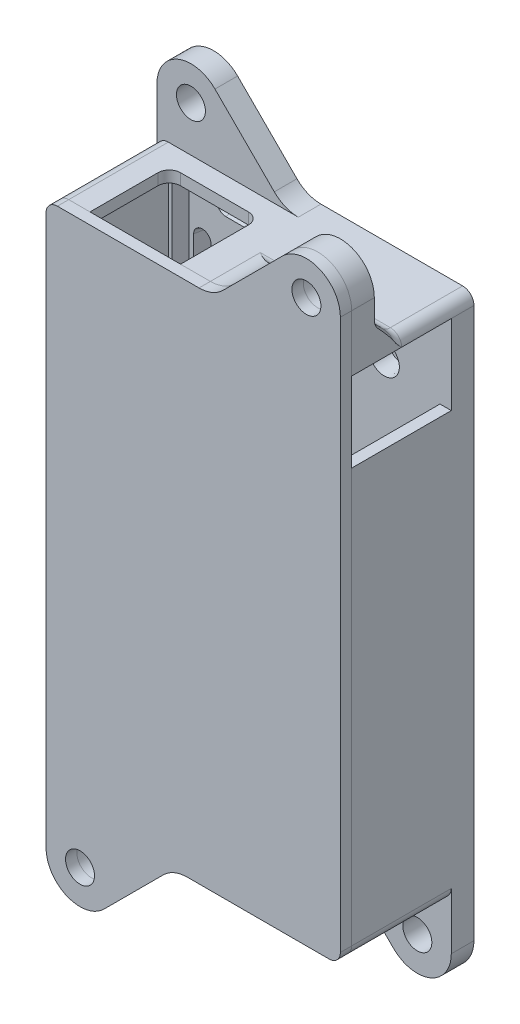
SolidWorks part; units mm, degrees
ref_plane "Front Plane" through (0, 0, 0) normal (0, 0, 1) x (1, 0, 0)
ref_plane "Top Plane" through (0, 0, 0) normal (0, 1, 0) x (1, 0, 0)
ref_plane "Right Plane" through (0, 0, 0) normal (1, 0, 0) x (0, 0, -1)
sketch "Sketch1" plane through (0, 0, 0) normal (0, 0, 1) x (1, 0, 0)
  line L1 (19.05, -34.6075) -> (-19.05, -34.6075)
  line L2 (19.05, -34.6075) -> (19.05, 34.6075)
  line L3 (19.05, 34.6075) -> (-19.05, 34.6075)
  line L4 (-19.05, -34.6075) -> (-19.05, 34.6075)
  line L5 (19.05, -34.6075) -> (-19.05, 34.6075) construction
  line L6 (19.05, 34.6075) -> (-19.05, -34.6075) construction
  point P0 (0, 0)
  dimension "D1" = 38.1
  dimension "D2" = 69.215
extrude "Boss-Extrude1" add sketch "Sketch1" along normal blind 3.175
sketch "Sketch2" plane through (0, 0, 0) normal (0, 0, -1) x (-1, 0, 0)
  line L0 (19.05, -34.6075) -> (19.05, -36.195) construction
  line L1 (-20.6375, 36.195) -> (20.6375, 36.195)
  line L2 (-20.6375, 36.195) -> (-20.6375, -36.195)
  line L3 (-20.6375, -36.195) -> (20.6375, -36.195)
  line L4 (19.05, -34.6075) -> (19.05, 34.6075)
  line L5 (19.05, 34.6075) -> (-19.05, 34.6075)
  line L6 (-19.05, 34.6075) -> (-19.05, -34.6075)
  line L7 (-19.05, -34.6075) -> (19.05, -34.6075)
  line L8 (19.05, -34.6075) -> (19.05, 34.6075)
  line L9 (19.05, 34.6075) -> (-19.05, 34.6075)
  line L10 (-19.05, 34.6075) -> (-19.05, -34.6075)
  line L11 (-19.05, -34.6075) -> (19.05, -34.6075)
  line L12 (20.6375, 36.195) -> (20.6375, -36.195)
  line L13 (-20.6375, 36.195) -> (20.6375, -36.195) construction
  line L14 (-20.6375, -36.195) -> (20.6375, 36.195) construction
  line L15 (19.05, -34.6075) -> (20.6375, -34.6075) construction
  point P2 (0, 0)
  dimension "D2" = 1.5875
  dimension "D1" = 0
extrude "Boss-Extrude2" add sketch "Sketch2" against normal blind 17.145
sketch "Sketch3" plane through (0, 0, 3.175) normal (0, 0, 1) x (1, 0, 0)
  line L0 (11.6785, -21.6089) -> (4.0585, -21.6089) construction
  line L1 (11.6785, -22.4027) -> (4.0585, -22.4027)
  line L2 (11.6785, -20.8152) -> (4.0585, -20.8152)
  line L3 (16.1685, -24.2089) -> (0.9285, -24.2089) construction
  line L4 (16.1685, -25.0027) -> (0.9285, -25.0027)
  line L5 (16.1685, -23.4152) -> (0.9285, -23.4152)
  line L6 (16.1685, -31.8289) -> (0.9285, -31.8289) construction
  line L7 (16.1685, -32.6227) -> (0.9285, -32.6227)
  line L8 (16.1685, -31.0352) -> (0.9285, -31.0352)
  line L9 (-2.0958, -25.2951) -> (-2.0958, 33.1249) construction
  line L10 (-2.8896, -25.2951) -> (-2.8896, -14.1826)
  line L11 (-1.3021, -25.2951) -> (-1.3021, 33.1249)
  line L12 (-17.3358, -25.2951) -> (-17.3358, 33.1249) construction
  line L13 (-18.1296, -25.2951) -> (-18.1296, 33.1249)
  line L14 (-16.5421, -25.2951) -> (-16.5421, -14.1826)
  line L15 (-14.285, 26.8257) -> (-14.285, 16.6657) construction
  line L16 (-13.4913, 26.8257) -> (-13.4913, 16.6657)
  line L17 (-15.0788, 26.8257) -> (-15.0788, 16.6657)
  line L18 (-6.5342, 20.1549) -> (-6.5342, 18.1549) construction
  line L19 (-10.9858, 32.3949) -> (-8.4458, 32.3949) construction
  line L20 (-4.5342, 17.3612) -> (-8.5342, 17.3612)
  line L21 (-3.7405, 18.1549) -> (-3.7405, 20.1549)
  line L22 (-4.5342, 20.9487) -> (-8.5342, 20.9487)
  line L23 (-9.328, 18.1549) -> (-9.328, 20.1549)
  line L24 (-3.7405, 17.3612) -> (-9.328, 20.9487) construction
  line L25 (-3.7405, 20.9487) -> (-9.328, 17.3612) construction
  line L26 (-10.9858, 33.1887) -> (-8.4458, 33.1887)
  line L27 (-10.9858, 31.6012) -> (-8.4458, 31.6012)
  line L28 (-16.5421, -11.0076) -> (-16.5421, 33.1249)
  line L29 (-15.7483, -11.8013) -> (-3.6833, -11.8013)
  line L31 (-15.7483, -13.3888) -> (-3.6833, -13.3888)
  line L33 (-16.5421, -11.8013) -> (-2.8896, -13.3888) construction
  line L34 (-16.5421, -13.3888) -> (-2.8896, -11.8013) construction
  line L35 (-2.8896, -11.0076) -> (-2.8896, 33.1249)
  line L36 (2.3316, 30.7906) -> (4.8716, 29.5206) construction
  line L37 (2.3316, 30.7906) -> (2.3316, 28.2506) construction
  line L38 (4.8716, 29.5206) -> (4.8716, 26.9806) construction
  line L39 (2.3316, 28.2506) -> (4.8716, 26.9806) construction
  line L40 (2.6866, 31.5006) -> (5.2266, 30.2306)
  line L41 (5.6654, 29.5206) -> (5.6654, 26.9806)
  line L42 (1.9766, 27.5407) -> (4.5166, 26.2707)
  line L43 (1.5379, 30.7906) -> (1.5379, 28.2506)
  line L44 (1.5379, 32.0749) -> (5.6654, 30.0112) construction
  line L45 (5.6654, 30.0112) -> (5.6654, 25.6963) construction
  line L46 (1.5379, 27.7601) -> (5.6654, 25.6963) construction
  line L47 (1.5379, 32.0749) -> (1.5379, 27.7601) construction
  arc A0 (11.6785, -22.4027) -> (11.6785, -20.8152) centre (11.6785, -21.6089) ccw
  arc A1 (4.0585, -20.8152) -> (4.0585, -22.4027) centre (4.0585, -21.6089) ccw
  arc A2 (16.1685, -25.0027) -> (16.1685, -23.4152) centre (16.1685, -24.2089) ccw
  arc A3 (0.9285, -23.4152) -> (0.9285, -25.0027) centre (0.9285, -24.2089) ccw
  arc A4 (16.1685, -32.6227) -> (16.1685, -31.0352) centre (16.1685, -31.8289) ccw
  arc A5 (0.9285, -31.0352) -> (0.9285, -32.6227) centre (0.9285, -31.8289) ccw
  arc A6 (-2.8896, -25.2951) -> (-1.3021, -25.2951) centre (-2.0958, -25.2951) ccw
  arc A7 (-1.3021, 33.1249) -> (-2.8896, 33.1249) centre (-2.0958, 33.1249) ccw
  arc A8 (-18.1296, -25.2951) -> (-16.5421, -25.2951) centre (-17.3358, -25.2951) ccw
  arc A9 (-16.5421, 33.1249) -> (-18.1296, 33.1249) centre (-17.3358, 33.1249) ccw
  arc A10 (-13.4913, 26.8257) -> (-15.0788, 26.8257) centre (-14.285, 26.8257) ccw
  arc A11 (-15.0788, 16.6657) -> (-13.4913, 16.6657) centre (-14.285, 16.6657) ccw
  arc A12 (-4.5342, 17.3612) -> (-3.7405, 18.1549) centre (-4.5342, 18.1549) ccw
  arc A13 (-8.5342, 17.3612) -> (-9.328, 18.1549) centre (-8.5342, 18.1549) cw
  arc A14 (-3.7405, 20.1549) -> (-4.5342, 20.9487) centre (-4.5342, 20.1549) ccw
  arc A15 (-8.5342, 20.9487) -> (-9.328, 20.1549) centre (-8.5342, 20.1549) ccw
  arc A16 (-10.9858, 33.1887) -> (-10.9858, 31.6012) centre (-10.9858, 32.3949) ccw
  arc A17 (-8.4458, 31.6012) -> (-8.4458, 33.1887) centre (-8.4458, 32.3949) ccw
  circle A18 centre (-4.6358, 30.5849) radius 0.7938
  arc A19 (5.2266, 30.2306) -> (5.6654, 29.5206) centre (4.8716, 29.5206) cw
  arc A20 (5.6654, 26.9806) -> (4.5166, 26.2707) centre (4.8716, 26.9806) cw
  arc A21 (1.9766, 27.5407) -> (1.5379, 28.2506) centre (2.3316, 28.2506) cw
  arc A22 (2.6866, 31.5006) -> (1.5379, 30.7906) centre (2.3316, 30.7906) ccw
  circle A23 centre (11.2216, 25.0706) radius 1.7145
  circle A24 centre (11.2216, 32.5706) radius 1.7145
  arc A25 (-3.6833, -11.8013) -> (-2.8896, -11.0076) centre (-3.6833, -11.0076) ccw
  arc A26 (-3.6833, -13.3888) -> (-2.8896, -14.1826) centre (-3.6833, -14.1826) cw
  arc A27 (-16.5421, -14.1826) -> (-15.7483, -13.3888) centre (-15.7483, -14.1826) cw
  arc A28 (-15.7483, -11.8013) -> (-16.5421, -11.0076) centre (-15.7483, -11.0076) cw
  point P4 (7.8685, -21.6089)
  point P9 (8.5485, -24.2089)
  point P20 (8.5485, -31.8289)
  point P49 (-14.285, 21.7457)
  point P54 (-6.5342, 19.1549)
  point P76 (-9.7158, 32.3949)
  point P85 (-9.7158, -12.5951)
  dimension "D1" = 0.7937
  dimension "D2" = 0.7937
  dimension "D3" = 1.5875
  dimension "D4" = 0.7938
  dimension "D6" = 0.7937
  dimension "D7" = 3.429
  dimension "D8" = 0.7937
  dimension "D5" = 0.7937
extrude "Cut-Extrude1" cut sketch "Sketch3" against normal blind 2.3813
chamfer "Chamfer1" distance 2.3813 angle 10 55 edges at (12.9361, 25.0706, 3.175) (12.9361, 32.5706, 3.175) (5.2889, 26.3054, 3.175) (5.6654, 28.2506, 3.175) (3.2466, 26.9057, 3.175) (5.5468, 29.9379, 3.175) (1.6564, 27.8333, 3.175) (3.9566, 30.8656, 3.175) (1.5379, 29.5206, 3.175) (1.9143, 31.4658, 3.175) (-6.5342, 17.3612, 3.175) (-3.973, 17.5937, 3.175) (-9.0955, 17.5937, 3.175) (-3.7405, 19.1549, 3.175) (-9.328, 19.1549, 3.175) (-3.973, 20.7162, 3.175) (-9.0955, 20.7162, 3.175) (-6.5342, 20.9487, 3.175) (-3.8421, 30.5849, 3.175) (-7.6521, 32.3949, 3.175) (-9.7158, 33.1887, 3.175) (-9.7158, 31.6012, 3.175) (-11.7796, 32.3949, 3.175) (-14.285, 15.872, 3.175) (-13.4913, 21.7457, 3.175) (-15.0788, 21.7457, 3.175) (-14.285, 27.6195, 3.175) (16.9623, -31.8289, 3.175) (8.5485, -31.0352, 3.175) (8.5485, -32.6227, 3.175) (0.1348, -31.8289, 3.175) (12.4723, -21.6089, 3.175) (7.8685, -20.8152, 3.175) (7.8685, -22.4027, 3.175) (3.2648, -21.6089, 3.175) (8.5485, -23.4152, 3.175) (0.1348, -24.2089, 3.175) (16.9623, -24.2089, 3.175) (8.5485, -25.0027, 3.175) (-2.0958, 33.9187, 3.175) (-2.8896, 11.0587, 3.175) (-1.3021, 3.9149, 3.175) (-3.1221, -11.5688, 3.175) (-2.0958, -26.0888, 3.175) (-9.7158, -11.8013, 3.175) (-2.8896, -19.7388, 3.175) (-16.3096, -11.5688, 3.175) (-3.1221, -13.6213, 3.175) (-16.5421, 11.0587, 3.175) (-9.7158, -13.3888, 3.175) (-17.3358, 33.9187, 3.175) (-16.3096, -13.6213, 3.175) (-18.1296, 3.9149, 3.175) (-16.5421, -19.7388, 3.175) (-17.3358, -26.0888, 3.175) first distance on face at (12.9361, 25.0706, 0.7937) first distance on face at (12.9361, 32.5706, 0.7937) first distance on face at (5.19, 26.4655, 1.9844) first distance on face at (5.6654, 28.2506, 1.9844) first distance on face at (3.2466, 26.9057, 1.9844) first distance on face at (5.4964, 29.9068, 1.9844) first distance on face at (1.7068, 27.8645, 1.9844) first distance on face at (3.9566, 30.8656, 1.9844) first distance on face at (1.5379, 29.5206, 1.9844) first distance on face at (2.0133, 31.3057, 1.9844) first distance on face at (-6.5342, 17.3612, 1.9844) first distance on face at (-4.0552, 17.6759, 1.9844) first distance on face at (-9.0133, 17.6759, 1.9844) first distance on face at (-3.7405, 19.1549, 1.9844) first distance on face at (-9.328, 19.1549, 1.9844) first distance on face at (-4.0552, 20.634, 1.9844) first distance on face at (-9.0133, 20.634, 1.9844) first distance on face at (-6.5342, 20.9487, 1.9844) first distance on face at (-3.8421, 30.5849, 0.7937) first distance on face at (-8.0489, 32.3949, 1.9844) first distance on face at (-9.7158, 33.1887, 1.9844) first distance on face at (-9.7158, 31.6012, 1.9844) first distance on face at (-11.3827, 32.3949, 1.9844) first distance on face at (-14.285, 16.2689, 1.9844) first distance on face at (-13.4913, 21.7457, 1.9844) first distance on face at (-15.0788, 21.7457, 1.9844) first distance on face at (-14.285, 27.2226, 1.9844) first distance on face at (16.5654, -31.8289, 1.9844) first distance on face at (8.5485, -31.0352, 1.9844) first distance on face at (8.5485, -32.6227, 1.9844) first distance on face at (0.5317, -31.8289, 1.9844) first distance on face at (12.0754, -21.6089, 1.9844) first distance on face at (7.8685, -20.8152, 1.9844) first distance on face at (7.8685, -22.4027, 1.9844) first distance on face at (3.6617, -21.6089, 1.9844) first distance on face at (8.5485, -23.4152, 1.9844) first distance on face at (0.5317, -24.2089, 1.9844) first distance on face at (16.5654, -24.2089, 1.9844) first distance on face at (8.5485, -25.0027, 1.9844) first distance on face at (-2.0958, 33.5218, 1.9844) first distance on face at (-2.8896, 11.0587, 1.9844) first distance on face at (-1.3021, 3.9149, 1.9844) first distance on face at (-3.2043, -11.4866, 1.9844) first distance on face at (-2.0958, -25.6919, 1.9844) first distance on face at (-9.7158, -11.8013, 1.9844) first distance on face at (-2.8896, -19.7388, 1.9844) first distance on face at (-16.2274, -11.4866, 1.9844) first distance on face at (-3.2043, -13.7035, 1.9844) first distance on face at (-16.5421, 11.0587, 1.9844) first distance on face at (-9.7158, -13.3888, 1.9844) first distance on face at (-17.3358, 33.5218, 1.9844) first distance on face at (-16.2274, -13.7035, 1.9844) first distance on face at (-18.1296, 3.9149, 1.9844) first distance on face at (-16.5421, -19.7388, 1.9844) first distance on face at (-17.3358, -25.6919, 1.9844)
sketch "Sketch4" plane through (19.05, 0, 0) normal (-1, 0, 0) x (0, 0, 1)
  line L0 (17.145, 34.6075) -> (17.145, -34.6075) construction
  line L1 (3.175, 34.6075) -> (17.145, 34.6075)
  line L2 (3.175, 34.6075) -> (3.175, 23.4315)
  line L3 (3.175, 23.4315) -> (17.145, 23.4315)
  line L4 (17.145, 34.6075) -> (17.145, 23.4315)
  dimension "D1" = 11.176
extrude "Cut-Extrude2" cut sketch "Sketch4" against normal through all
sketch "Sketch5" plane through (0, -34.6075, 0) normal (0, 1, 0) x (1, 0, 0)
  line L1 (-3.5719, -8.7312) -> (-18.6531, -8.7312)
  line L2 (-3.5719, -8.7312) -> (-3.5719, -3.9687)
  line L3 (-3.5719, -3.9687) -> (-18.6531, -3.9687)
  line L4 (-18.6531, -8.7312) -> (-18.6531, -3.9687)
  line L5 (-3.5719, -8.7312) -> (-18.6531, -3.9687) construction
  line L6 (-3.5719, -3.9687) -> (-18.6531, -8.7312) construction
  line L7 (-19.05, -17.145) -> (-19.05, -3.175) construction
  line L8 (-19.05, -3.175) -> (19.05, -3.175) construction
  point P0 (-11.1125, -6.35)
  dimension "D1" = 3.175
  dimension "D2" = 0.3969
  dimension "D3" = 15.0812
  dimension "D4" = 4.7625
extrude "Cut-Extrude3" cut sketch "Sketch5" against normal through all
fillet "Fillet1" radius 0.7937 4 edges at (-18.6531, -35.4012, 8.7312) (-3.5719, -35.4012, 8.7312) (-3.5719, -35.4012, 3.9687) (-18.6531, -35.4012, 3.9687)
sketch "Sketch6" plane through (0, 0, 3.175) normal (0, 0, 1) x (1, 0, 0)
  circle A0 centre (10.3042, -9.0151) radius 1.6 construction
  circle A3 centre (10.3042, -9.0151) radius 1.6
extrude "Cut-Extrude4" cut sketch "Sketch6" against normal through all contours A3
sketch "Sketch7" plane through (0, 0, 0) normal (0, 0, -1) x (-1, 0, 0)
  line L0 (-20.6375, -36.195) -> (-20.6375, -42.545)
  line L1 (-12.5074, -45.9126) -> (-4.1847, -37.5899)
  line L2 (-20.6375, -36.195) -> (20.6375, -36.195) construction
  line L3 (-20.6375, -36.195) -> (-0.8171, -36.195)
  line L4 (20.6375, 36.195) -> (0.8171, 36.195)
  line L5 (20.6375, 36.195) -> (-20.6375, 36.195) construction
  line L6 (4.1847, 37.5899) -> (12.5074, 45.9126)
  line L7 (20.6375, 42.545) -> (20.6375, 36.195)
  arc A0 (-20.6375, -42.545) -> (-12.5074, -45.9126) centre (-15.875, -42.545) ccw
  arc A1 (-4.1847, -37.5899) -> (-0.8171, -36.195) centre (-0.8171, -40.9575) cw
  circle A2 centre (-15.875, -42.545) radius 2.032
  arc A3 (0.8171, 36.195) -> (4.1847, 37.5899) centre (0.8171, 40.9575) ccw
  arc A4 (12.5074, 45.9126) -> (20.6375, 42.545) centre (15.875, 42.545) cw
  circle A5 centre (15.875, 42.545) radius 2.032
  dimension "D2" = 4.7625
  dimension "D4" = 4.064
  dimension "D1" = 6.35
  dimension "D3" = 45
  dimension "D5" = 6.35
  dimension "D6" = 45
extrude "Boss-Extrude3" add sketch "Sketch7" against normal blind 3.175
sketch "Sketch9" plane through (0, 0, 17.145) normal (0, 0, 1) x (1, 0, 0)
  line L0 (-20.6375, -36.195) -> (-20.6375, -42.545)
  line L1 (-12.5074, -45.9126) -> (-4.1847, -37.5899)
  line L2 (20.6375, -36.195) -> (-20.6375, -36.195) construction
  line L3 (-15.875, -42.545) -> (15.875, -42.545) construction
  line L4 (-0.8171, -36.195) -> (-20.6375, -36.195)
  line L5 (20.6375, 36.195) -> (20.6375, 42.545)
  line L6 (12.5074, 45.9126) -> (4.1847, 37.5899)
  line L7 (-20.6375, 36.195) -> (20.6375, 36.195) construction
  line L8 (0.8171, 36.195) -> (20.6375, 36.195)
  arc A0 (-20.6375, -42.545) -> (-12.5074, -45.9126) centre (-15.875, -42.545) ccw
  arc A1 (-4.1847, -37.5899) -> (-0.8171, -36.195) centre (-0.8171, -40.9575) cw
  arc A2 (12.5074, -45.9126) -> (20.6375, -42.545) centre (15.875, -42.545) ccw construction
  circle A3 centre (-15.875, -42.545) radius 2.032
  circle A4 centre (15.875, -42.545) radius 2.032 construction
  arc A5 (20.6375, 42.545) -> (12.5074, 45.9126) centre (15.875, 42.545) ccw
  arc A6 (4.1847, 37.5899) -> (0.8171, 36.195) centre (0.8171, 40.9575) cw
  arc A7 (-4.1847, 37.5899) -> (-0.8171, 36.195) centre (-0.8171, 40.9575) ccw construction
  circle A8 centre (15.875, 42.545) radius 2.032
  circle A9 centre (-15.875, 42.545) radius 2.032 construction
  dimension "D1" = 45
  dimension "D2" = 45
extrude "Boss-Extrude4" add sketch "Sketch9" against normal blind 3.175
fillet "Fillet3" radius 1.5875 4 edges at (-20.6375, -36.195, 6.985) (20.6375, -36.195, 10.16) (-20.6375, 36.195, 10.16) (20.6375, 36.195, 6.985)
chamfer "Chamfer2" distance 3.175 angle 45 4 edges at (-9.9336, -36.195, 13.97) (9.9336, 36.195, 13.97) (-20.1725, -35.73, 13.97) (20.1725, 35.73, 13.97)
fillet "Fillet2" radius 1.5875 8 edges at (12.5074, 39.37, 13.97) (9.9336, 36.195, 10.795) (-12.5074, -39.37, 13.97) (-9.9336, -36.195, 10.795) (19.8553, 39.3014, 13.97) (20.1725, 35.73, 10.795) (-19.8553, -39.3014, 13.97) (-20.1725, -35.73, 10.795)
sketch "Sketch10" plane through (0, 0, 17.145) normal (0, 0, 1) x (1, 0, 0)
  line L0 (-12.5074, -45.9126) -> (-4.1847, -37.5899) construction
  line L3 (20.6375, 42.545) -> (20.6375, 34.6075) construction
  line L4 (12.5074, 45.9126) -> (4.1847, 37.5899) construction
  line L8 (-12.5074, -45.9126) -> (-4.1847, -37.5899)
  line L11 (20.6375, 42.545) -> (20.6375, 34.6075)
  line L12 (12.5074, 45.9126) -> (4.1847, 37.5899)
  line L16 (20.6375, 34.6075) -> (20.6375, 23.4315)
  line L19 (19.05, -36.195) -> (-0.8171, -36.195) construction
  line L20 (19.05, -36.195) -> (-0.8171, -36.195)
  line L21 (20.6375, 23.4315) -> (20.6375, -34.6075) construction
  line L22 (20.6375, 23.4315) -> (20.6375, -34.6075)
  line L23 (-20.6375, -42.545) -> (-20.6375, 34.6075) construction
  line L24 (-19.05, 36.195) -> (0.8171, 36.195) construction
  line L25 (-20.6375, -42.545) -> (-20.6375, 34.6075)
  line L26 (-19.05, 36.195) -> (0.8171, 36.195)
  arc A0 (-20.6375, -42.545) -> (-12.5074, -45.9126) centre (-15.875, -42.545) ccw construction
  arc A1 (-0.8171, -36.195) -> (-4.1847, -37.5899) centre (-0.8171, -40.9575) ccw construction
  arc A2 (20.6375, 42.545) -> (12.5074, 45.9126) centre (15.875, 42.545) ccw construction
  arc A3 (0.8171, 36.195) -> (4.1847, 37.5899) centre (0.8171, 40.9575) ccw construction
  arc A4 (-20.6375, -42.545) -> (-12.5074, -45.9126) centre (-15.875, -42.545) ccw
  arc A5 (-0.8171, -36.195) -> (-4.1847, -37.5899) centre (-0.8171, -40.9575) ccw
  arc A6 (20.6375, 42.545) -> (12.5074, 45.9126) centre (15.875, 42.545) ccw
  arc A7 (0.8171, 36.195) -> (4.1847, 37.5899) centre (0.8171, 40.9575) ccw
  circle A8 centre (15.875, 42.545) radius 2.032 construction
  circle A9 centre (-15.875, -42.545) radius 2.032 construction
  circle A10 centre (15.875, 42.545) radius 2.032
  circle A11 centre (-15.875, -42.545) radius 2.032
  arc A12 (19.05, -36.195) -> (20.6375, -34.6075) centre (19.05, -34.6075) ccw construction
  arc A13 (19.05, -36.195) -> (20.6375, -34.6075) centre (19.05, -34.6075) ccw
  arc A14 (-19.05, 36.195) -> (-20.6375, 34.6075) centre (-19.05, 34.6075) ccw construction
  arc A15 (-19.05, 36.195) -> (-20.6375, 34.6075) centre (-19.05, 34.6075) ccw
extrude "Boss-Extrude5" add sketch "Sketch10" along normal blind 1.5875 separate body
sketch "Sketch11" plane through (0, 0, 17.145) normal (0, 0, 1) x (1, 0, 0)
  line L0 (-17.3358, 33.1249) -> (-2.0958, 33.1249) construction
  line L1 (-9.7158, 33.1249) -> (-9.7158, 35.4013) construction
  line L2 (-0.8171, 36.195) -> (-19.05, 36.195) construction
  line L3 (-16.0658, 34.6075) -> (-3.3658, 34.6075)
  line L4 (-16.0658, 34.6075) -> (-16.0658, 36.195)
  line L5 (-16.0658, 36.195) -> (-3.3658, 36.195)
  line L6 (-3.3658, 34.6075) -> (-3.3658, 36.195)
  line L7 (-16.0658, 34.6075) -> (-3.3658, 36.195) construction
  line L8 (-16.0658, 36.195) -> (-3.3658, 34.6075) construction
  line L9 (10.5839, 34.6075) -> (-19.05, 34.6075) construction
  dimension "D1" = 12.7
extrude "Cut-Extrude5" cut sketch "Sketch11" against normal blind 11.1125
fillet "Fillet4" radius 1.5875 2 edges at (-3.3658, 35.4013, 6.0325) (-16.0658, 35.4013, 6.0325)
equation "\"D5@Sketch7\"=\"D1@Sketch7\""
equation "\"D6@Sketch7\"=\"D3@Sketch7\""
equation "\"D2@Sketch9\"=\"D1@Sketch9\""
